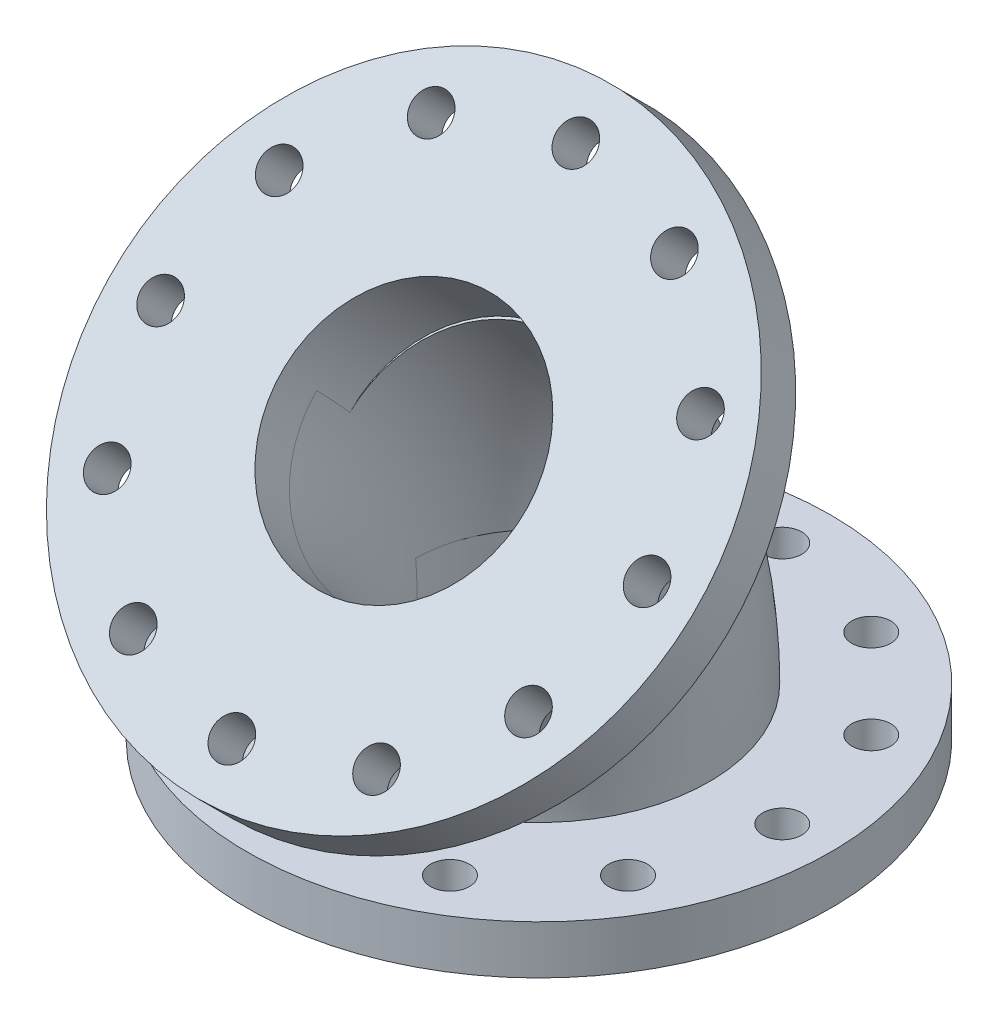
SolidWorks part; units mm, degrees
note: The reader was unsure of these and kept them because the rebuilt part matched: shared geometry of "Sketch16<3>", "Sketch21<3>", "Sketch22<3>".
ref_plane "Front Plane" through (0, 0, 0) normal (0, 0, 1) x (1, 0, 0)
ref_plane "Top Plane" through (0, 0, 0) normal (0, 1, 0) x (1, 0, 0)
ref_plane "Right Plane" through (0, 0, 0) normal (1, 0, 0) x (0, 0, -1)
sketch "Sketch15" plane through (0, 0, 0) normal (0, 0, 1) x (1, 0, 0)
sketch "Sketch16" plane through (0, 0, 0) normal (1, 0, 0) x (0, 0, -1)
  line L0 (-1000, 0) -> (49000, 0) construction
  line L1 (-100, 0) -> (-29.2893, 70.7107) construction
  arc A0 (0, 0) -> (-29.2893, 70.7107) centre (-100, 0) ccw
  dimension "D2" = 100
  dimension "D1" = 45
sketch "Sketch17" plane through (0, 0, 0) normal (0, 1, 0) x (1, 0, 0)
  line L0 (0, -29.2893) -> (0, 0) construction
  line L1 (0, -201000) -> (0, 249000) construction
  circle A0 centre (0, -29.2893) radius 35
  dimension "D1" = 70
sweep "Sweep1" add profiles "Sketch17" path "Sketch16"
ref_plane "Plane1" through (0, 0, 0) normal (0, -1, 0) x (-1, 0, 0)
sketch "Sketch18" plane through (0, 0, 0) normal (0, -1, 0) x (-1, 0, 0)
  circle A0 centre (0, -29.2893) radius 60
  dimension "D1" = 120
extrude "Boss-Extrude2" add sketch "Sketch18" along normal blind 10
ref_plane "Plane2" through (0, 50, 50) normal (0, 0.7071, 0.7071) x (1, 0, 0)
sketch "Sketch19" plane through (0, 50, 50) normal (0, 0.7071, 0.7071) x (1, 0, 0)
  circle A0 centre (0, 0) radius 60
  dimension "D1" = 120
extrude "Boss-Extrude3" add sketch "Sketch19" along normal blind 10
sketch "Sketch20" plane through (0, 0, 0) normal (0, -1, 0) x (-1, 0, 0)
  line L0 (0, -1029.2893) -> (0, 48970.7107) construction
  circle A0 centre (0, -29.2893) radius 50 construction
  circle A1 centre (0, -29.2893) radius 60 construction
  circle A2 centre (0, 20.7107) radius 4
  circle A3 centre (25, 14.0119) radius 4
  circle A4 centre (43.3013, -4.2893) radius 4
  circle A5 centre (50, -29.2893) radius 4
  circle A6 centre (43.3013, -54.2893) radius 4
  circle A7 centre (25, -72.5906) radius 4
  circle A8 centre (0, -79.2893) radius 4
  circle A9 centre (-25, -72.5906) radius 4
  circle A10 centre (-43.3013, -54.2893) radius 4
  circle A11 centre (-50, -29.2893) radius 4
  circle A12 centre (-43.3013, -4.2893) radius 4
  circle A13 centre (-25, 14.0119) radius 4
  point P33 (0, -29.2893)
  dimension "D1" = 100
  dimension "D2" = 8
  dimension "D4" = 25
  dimension "D3" = 12
extrude "Cut-Extrude1" cut sketch "Sketch20" against normal blind 10 and the other way through all
sketch "Sketch21" plane through (0, 0, 0) normal (0, -1, 0) x (-1, 0, 0)
  circle A0 centre (0, -29.2893) radius 25
  circle A1 centre (0, -29.2893) radius 60 construction
  dimension "D1" = 50
sweep "Cut-Sweep2" cut profiles "Sketch21" path "Sketch16<3>"
sketch "Sketch16<3>" plane through (0, 0, 0) normal (1, 0, 0) x (0, 0, -1) same geometry as "Sketch16"
extrude "Cut-Extrude3" cut sketch "Sketch21<3>" against normal blind 10 and the other way through all
sketch "Sketch21<3>" plane through (0, 0, 0) normal (0, -1, 0) x (-1, 0, 0) same geometry as "Sketch21"
sketch "Sketch22" plane through (0, 50, 50) normal (0, 0.7071, 0.7071) x (1, 0, 0)
  circle A0 centre (0, 0) radius 25
  dimension "D1" = 50
extrude "Cut-Extrude10" cut sketch "Sketch22" against normal blind 10
extrude "Cut-Extrude11" cut sketch "Sketch22<3>" along normal blind 10
sketch "Sketch22<3>" plane through (0, 50, 50) normal (0, 0.7071, 0.7071) x (1, 0, 0) same geometry as "Sketch22"
sketch "Sketch24" plane through (0, 50, 50) normal (0, 0.7071, 0.7071) x (1, 0, 0)
  line L0 (0, -1000) -> (0, 49000) construction
  circle A0 centre (0, 0) radius 50 construction
  circle A1 centre (0, 50) radius 4
  circle A2 centre (25, 43.3013) radius 4
  circle A3 centre (43.3013, 25) radius 4
  circle A4 centre (50, 0) radius 4
  circle A5 centre (43.3013, -25) radius 4
  circle A6 centre (25, -43.3013) radius 4
  circle A7 centre (0, -50) radius 4
  circle A8 centre (-25, -43.3013) radius 4
  circle A9 centre (-43.3013, -25) radius 4
  circle A10 centre (-50, 0) radius 4
  circle A11 centre (-43.3013, 25) radius 4
  circle A12 centre (-25, 43.3013) radius 4
  point P31 (0, 0)
  dimension "D1" = 100
  dimension "D2" = 8
  dimension "D3" = 12
extrude "Cut-Extrude18" cut sketch "Sketch24" along normal blind 10
